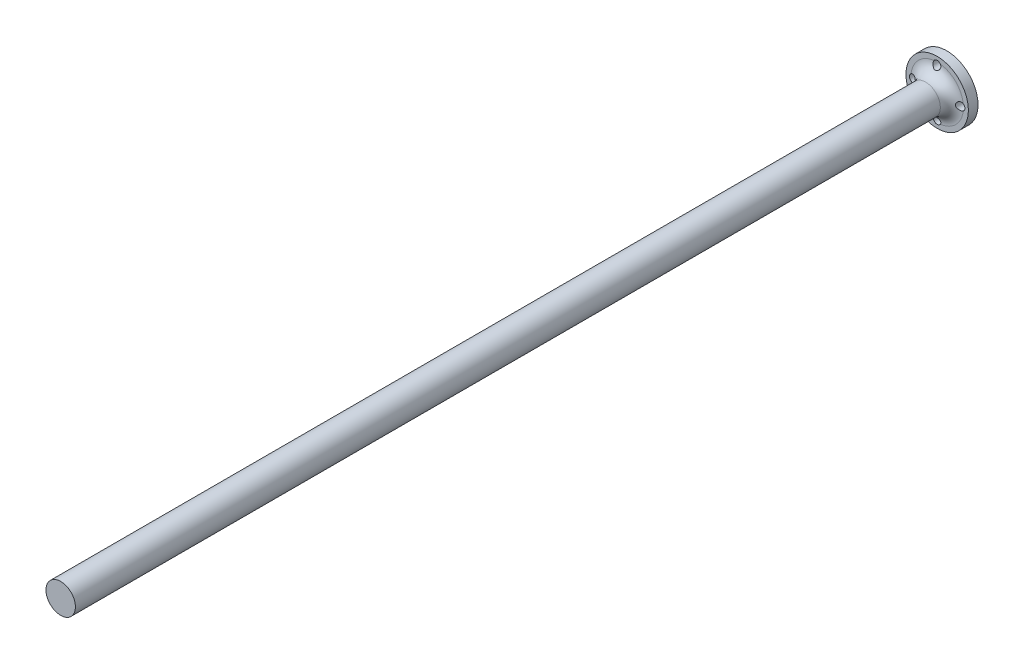
SolidWorks part; units mm, degrees
ref_plane "Front Plane" through (0, 0, 0) normal (0, 0, 1) x (1, 0, 0)
ref_plane "Top Plane" through (0, 0, 0) normal (0, 1, 0) x (1, 0, 0)
ref_plane "Right Plane" through (0, 0, 0) normal (1, 0, 0) x (0, 0, -1)
sketch "Sketch1" plane through (0, 0, 0) normal (0, 0, 1) x (1, 0, 0)
  circle A0 centre (0, 0) radius 10.287
  dimension "D1" = 20.574
extrude "Boss-Extrude1" add sketch "Sketch1" along normal blind 3.175
sketch "Sketch2" plane through (0, 0, 3.175) normal (0, 0, 1) x (1, 0, 0)
  circle A0 centre (0, 0) radius 4.8514
  dimension "D1" = 9.7028
extrude "Boss-Extrude2" add sketch "Sketch2" along normal blind 288.925
sketch "Sketch3" plane through (0, 0, 0) normal (0, 0, -1) x (-1, 0, 0)
  circle A0 centre (0, 0) radius 4.064
  dimension "D1" = 8.128
extrude "Cut-Extrude1" cut sketch "Sketch3" against normal blind 1.27
fillet "Fillet1" radius 1 1 edges at (-4.064, 0, 0)
sketch "Sketch4" plane through (0, 0, 0) normal (0, 0, -1) x (-1, 0, 0)
  circle A0 centre (0, 7.874) radius 1.27
  dimension "D1" = 2.54
  dimension "D2" = 7.874
extrude "Cut-Extrude2" cut sketch "Sketch4" against normal up to next
pattern_circular "CirPattern1" count 4 over 360 about axis through (0, 0, 3.175) along (0, 0, -1) of "Cut-Extrude2"
fillet "Fillet2" radius 3.81 1 edges at (4.8514, 0, 3.175)
